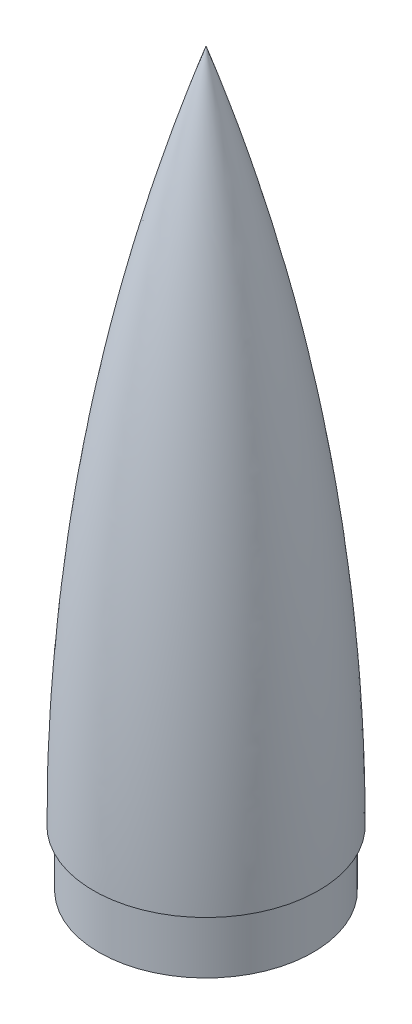
SolidWorks part; units mm, degrees
ref_plane "Front Plane" through (0, 0, 0) normal (0, 0, 1) x (1, 0, 0)
ref_plane "Top Plane" through (0, 0, 0) normal (0, 1, 0) x (1, 0, 0)
ref_plane "Right Plane" through (0, 0, 0) normal (1, 0, 0) x (0, 0, -1)
sketch "Sketch1" plane through (0, 0, 0) normal (0, 0, 1) x (1, 0, 0)
  line L0 (0, 0) -> (0, 152.4) construction
  line L1 (-25.4, 0) -> (444.5, 0) construction
  line L2 (-25.4, 0) -> (-24.1554, 0)
  line L3 (-24.1554, 0) -> (-24.1554, -12.7)
  line L4 (-24.1554, -12.7) -> (0, -12.7)
  line L6 (0, -12.7) -> (0, 152.4)
  arc A0 (-25.4, 0) -> (0, 152.4) centre (444.5, 0) cw
  dimension "D1" = 50.8
  dimension "D2" = 152.4
  dimension "D3" = 48.3108
  dimension "D4" = 12.7
revolve "Revolve1" add sketch "Sketch1" angle 360 about L6
